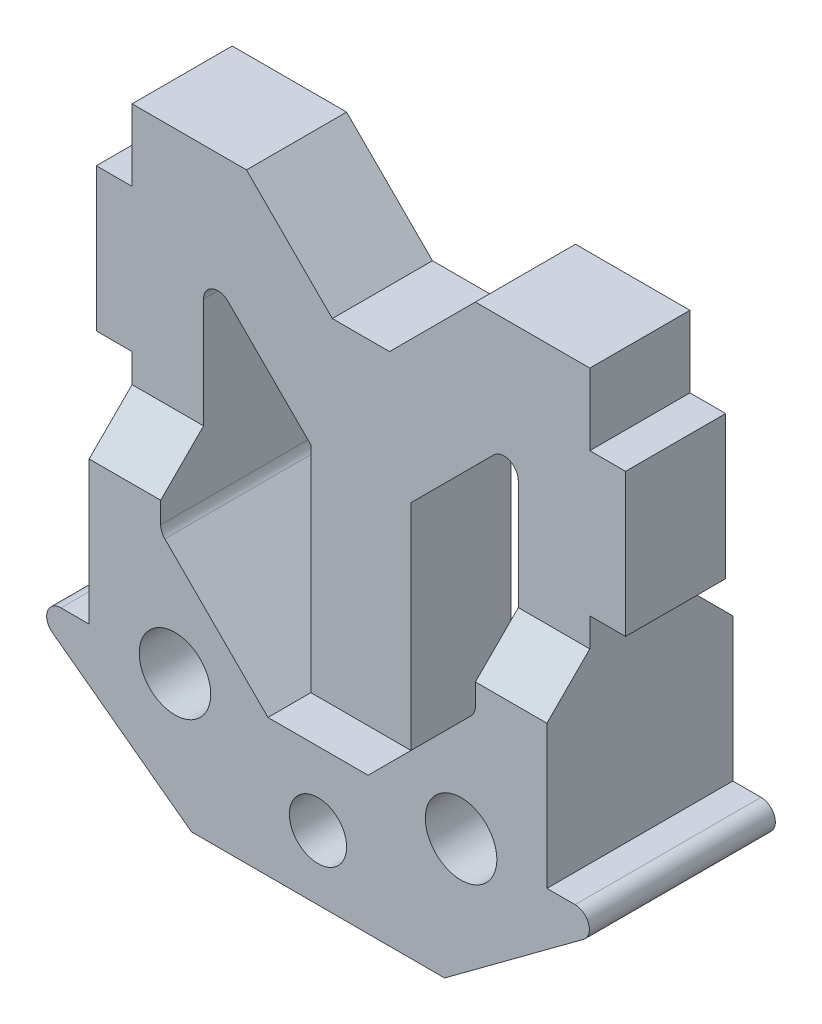
SolidWorks part; units mm, degrees
note: The reader was unsure of these and kept them because the rebuilt part matched: shared geometry of "Esquisse4<4>".
ref_plane "Plan de face" through (0, 0, 0) normal (0, 0, 1) x (1, 0, 0)
ref_plane "Plan de dessus" through (0, 0, 0) normal (0, 1, 0) x (1, 0, 0)
ref_plane "Plan de droite" through (0, 0, 0) normal (1, 0, 0) x (0, 0, -1)
sketch "Esquisse1" plane through (0, 0, 0) normal (0, 0, 1) x (1, 0, 0)
  line L0 (-16, 6) -> (-8, 6)
  line L1 (-8, 6) -> (-2, 0)
  line L2 (-2, 0) -> (2, 0)
  line L3 (16, -24) -> (16, 6)
  line L4 (21, -24) -> (16, -24)
  line L5 (7.5, -34) -> (21, -24)
  line L6 (7.5, -34) -> (-7.5, -34)
  line L7 (-7.5, -34) -> (-21, -24)
  line L8 (-21, -24) -> (-16, -24)
  line L9 (-16, -24) -> (-16, 6)
  line L10 (2, 0) -> (8, 6)
  line L11 (8, 6) -> (16, 6)
  line L12 (0, -1000) -> (0, 49000) construction
  line L13 (-18.5, 1) -> (-18.5, -9)
  line L14 (16, 1) -> (18.5, 1)
  line L15 (16, 1) -> (16, -9)
  line L16 (16, -9) -> (18.5, -9)
  line L17 (18.5, 1) -> (18.5, -9)
  line L18 (-16, -9) -> (-18.5, -9)
  line L19 (-16, 1) -> (-16, -9)
  line L20 (-16, 1) -> (-18.5, 1)
  point P17 (0, -34)
  dimension "D1" = 5
  dimension "D2" = 135
  dimension "D3" = 8
  dimension "D4" = 15
  dimension "D5" = 10
  dimension "D6" = 32
  dimension "D7" = 8
  dimension "D8" = 4
  dimension "D9" = 30
  dimension "D10" = 2.5
  dimension "D11" = 10
  dimension "D12" = 15
extrude "Boss.-Extru.1" add sketch "Esquisse1" along normal blind 7 contours L6 L12 L2 L1 L0 L9 L8 L7 | L12 L6 L5 L4 L3 L11 L10 L2 | L17 L14 L3 L16 | L9 L20 L13 L18
sketch "Esquisse2" plane through (0, 0, 7) normal (0, 0, 1) x (1, 0, 0)
  line L0 (-16, -14) -> (16, -14)
  line L20 (-7.5, -34) -> (7.5, -34)
  line L21 (7.5, -34) -> (21, -24)
  line L22 (21, -24) -> (16, -24)
  line L23 (16, -24) -> (16, -9)
  line L24 (16, -9) -> (18.5, -9)
  line L25 (18.5, -9) -> (18.5, 1)
  line L26 (18.5, 1) -> (16, 1)
  line L27 (16, 1) -> (16, 6)
  line L28 (16, 6) -> (8, 6)
  line L29 (8, 6) -> (2, 0)
  line L30 (2, 0) -> (-2, 0)
  line L31 (-2, 0) -> (-8, 6)
  line L32 (-8, 6) -> (-16, 6)
  line L33 (-16, 6) -> (-16, 1)
  line L34 (-16, 1) -> (-18.5, 1)
  line L35 (-18.5, 1) -> (-18.5, -9)
  line L36 (-18.5, -9) -> (-16, -9)
  line L37 (-16, -9) -> (-16, -24)
  line L38 (-16, -24) -> (-21, -24)
  line L39 (-21, -24) -> (-7.5, -34)
  line L40 (-7.5, -34) -> (7.5, -34)
  line L41 (7.5, -34) -> (21, -24)
  line L42 (21, -24) -> (16, -24)
  line L43 (16, -24) -> (16, -9)
  line L44 (16, -9) -> (18.5, -9)
  line L45 (18.5, -9) -> (18.5, 1)
  line L46 (18.5, 1) -> (16, 1)
  line L47 (16, 1) -> (16, 6)
  line L48 (16, 6) -> (8, 6)
  line L49 (8, 6) -> (2, 0)
  line L50 (2, 0) -> (-2, 0)
  line L51 (-2, 0) -> (-8, 6)
  line L52 (-8, 6) -> (-16, 6)
  line L53 (-16, 6) -> (-16, 1)
  line L54 (-16, 1) -> (-18.5, 1)
  line L55 (-18.5, 1) -> (-18.5, -9)
  line L56 (-18.5, -9) -> (-16, -9)
  line L57 (-16, -9) -> (-16, -24)
  line L58 (-16, -24) -> (-21, -24)
  line L59 (-21, -24) -> (-7.5, -34)
  dimension "D2" = 20
  dimension "D1" = 0
extrude "Boss.-Extru.2" add sketch "Esquisse2" along normal blind 3 and the other way offset from surface (10 mm away) 3 contours L58 L59 L40 L41 L42 L43 L0 L57 other way up to face at (0, -8.6, 0)
sketch "Esquisse3" plane through (0, 0, -3) normal (0, 0, -1) x (-1, 0, 0)
  line L0 (-11, -0.8995) -> (-3.5, -8.3995)
  line L1 (-3.5, -8.3995) -> (-3.5, -23.3995)
  line L2 (-3.5, -23.3995) -> (-11, -15.8995)
  line L3 (-11, -15.8995) -> (-11, -0.8995)
  line L4 (0, -1000) -> (0, 49000) construction
  line L5 (11, -15.8995) -> (11, -0.8995)
  line L6 (3.5, -23.3995) -> (11, -15.8995)
  line L7 (3.5, -8.3995) -> (3.5, -23.3995)
  line L8 (11, -0.8995) -> (3.5, -8.3995)
  line L14 (-2, 0) -> (-8, 6) construction
  line L15 (-16, 1) -> (-16, 6) construction
  dimension "D1" = 7
  dimension "D2" = 5
  dimension "D3" = 7
  dimension "D4" = 15
extrude "Enlèv. mat.-Extru.1" cut sketch "Esquisse3" against normal up to next
sketch "Esquisse4" plane through (0, 0, -3) normal (0, 0, -1) x (-1, 0, 0)
  line L1 (-3.5, -14) -> (3.5, -14)
  line L2 (-3.5, -14) -> (-3.5, -23.3995)
  line L3 (-3.5, -23.3995) -> (3.5, -23.3995)
  line L4 (3.5, -14) -> (3.5, -23.3995)
extrude "Enlèv. mat.-Extru.4" cut sketch "Esquisse4<4>" against normal up to surface (3 mm away) up to face at (0, -4.6082, 0)
sketch "Esquisse4<4>" plane through (0, 0, -3) normal (0, 0, -1) x (-1, 0, 0) same geometry as "Esquisse4"
extrude "Enlèv. mat.-Extru.2" cut sketch "Esquisse4" along normal up to surface (3 mm away) from surface at -13 up to face at (0, -4.6082, 7) starting at face at (0, -20.4124, 10)
chamfer "Chanfrein1" distance 3 angle 45 4 edges at (-13.5, -14, 0) (-13.5, -14, 7) (13.5, -14, 0) (13.5, -14, 7)
fillet "Congé1" radius 1 6 edges at (11, -15.8995, 3.5) (-11, -15.8995, 3.5) (11, -0.8995, 3.5) (-11, -0.8995, 3.5) (21, -24, 3.5) (-21, -24, 3.5)
sketch "Esquisse5" plane through (0, -34, 0) normal (0, -1, 0) x (1, 0, 0)
  line L0 (-7.5, 10) -> (7.5, -3) construction
  circle A0 centre (0, 3.5) radius 4.8
  dimension "D1" = 9.6
extrude "Enlèv. mat.-Extru.5" cut sketch "Esquisse5" against normal blind 1
sketch "Esquisse6" plane through (0, 0, 10) normal (0, 0, 1) x (1, 0, 0)
  line L0 (0, -1000) -> (0, 49000) construction
  line L1 (-7.5, -34) -> (7.5, -34) construction
  circle A0 centre (-10, -24) radius 2.5
  circle A1 centre (0, -28.5) radius 2
  circle A2 centre (10, -24) radius 2.5
  dimension "D1" = 5
  dimension "D2" = 4
  dimension "D3" = 5.5
  dimension "D4" = 10
  dimension "D5" = 10
extrude "Enlèv. mat.-Extru.6" cut sketch "Esquisse6" against normal through all
chamfer "Chanfrein2" distance 1 angle 45 2 edges at (0, -34, -3) (0, -34, 10)
